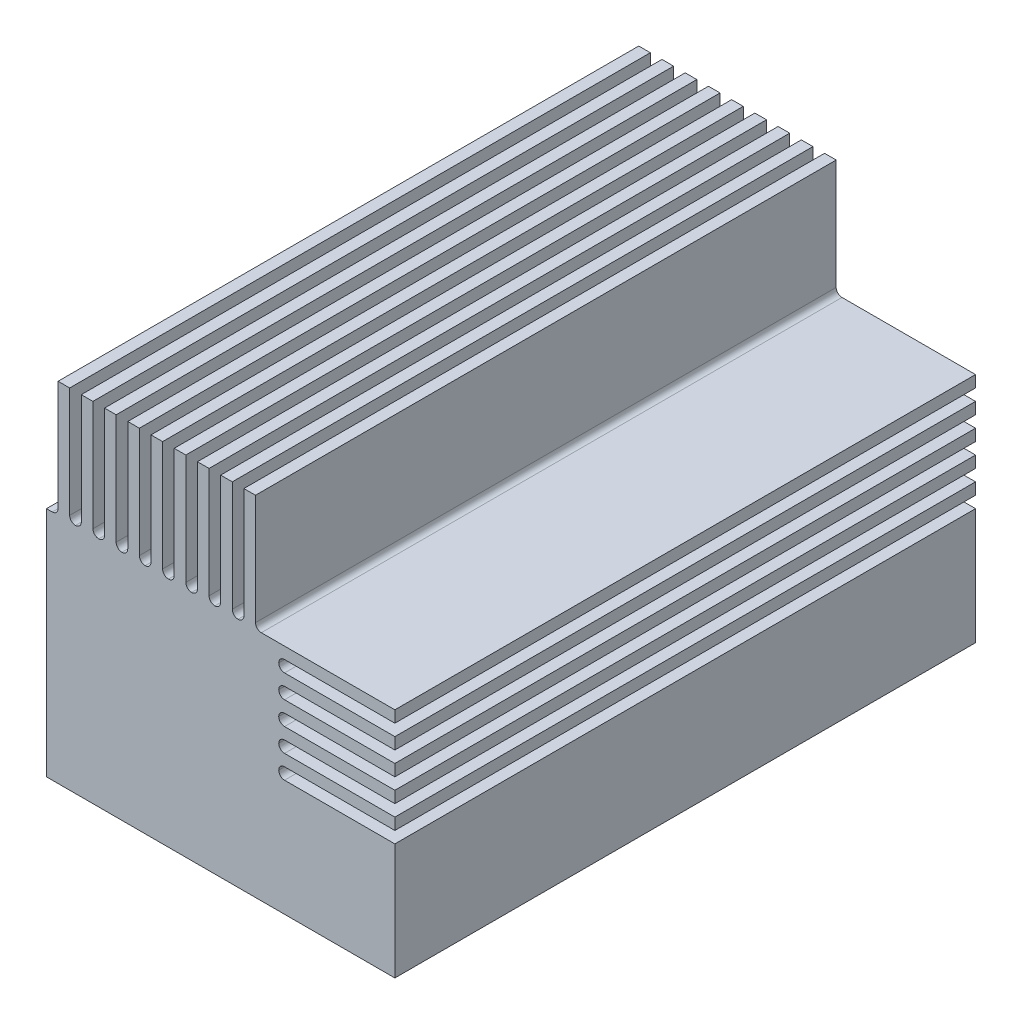
SolidWorks part; units mm, degrees
ref_plane "Front Plane" through (0, 0, 0) normal (0, 0, 1) x (1, 0, 0)
ref_plane "Top Plane" through (0, 0, 0) normal (0, 1, 0) x (1, 0, 0)
ref_plane "Right Plane" through (0, 0, 0) normal (1, 0, 0) x (0, 0, -1)
sketch "Sketch1" plane through (0, 0, 0) normal (0, 1, 0) x (1, 0, 0)
  line L1 (0, 0) -> (100, 0)
  line L2 (0, 0) -> (0, 250)
  line L3 (0, 250) -> (100, 250)
  line L4 (100, 0) -> (100, 250)
  dimension "D1" = 100
  dimension "D2" = 250
extrude "Boss-Extrude1" add sketch "Sketch1" along normal blind 100
sketch "Sketch2" plane through (0, 0, 0) normal (0, 0, 1) x (1, 0, 0)
  line L41 (100, 90) -> (100, 85)
  line L42 (100, 100) -> (150, 100)
  line L43 (100, 100) -> (100, 95)
  line L44 (100, 95) -> (150, 95)
  line L45 (150, 100) -> (150, 95)
  line L46 (100, 90) -> (150, 90)
  line L47 (150, 90) -> (150, 85)
  line L48 (100, 85) -> (150, 85)
  line L49 (100, 80) -> (100, 75)
  line L50 (100, 80) -> (150, 80)
  line L51 (150, 80) -> (150, 75)
  line L52 (100, 75) -> (150, 75)
  line L53 (100, 70) -> (100, 65)
  line L54 (0, 100) -> (5, 100) construction
  line L55 (0, 100) -> (100, 100) construction
  line L56 (15, 100) -> (15, 150)
  line L57 (5, 100) -> (10, 100)
  line L58 (5, 100) -> (5, 150)
  line L59 (5, 150) -> (10, 150)
  line L60 (10, 100) -> (10, 150)
  line L61 (15, 100) -> (20, 100)
  line L62 (20, 100) -> (20, 150)
  line L63 (15, 150) -> (20, 150)
  line L64 (25, 100) -> (25, 150)
  line L65 (25, 100) -> (30, 100)
  line L66 (30, 100) -> (30, 150)
  line L67 (25, 150) -> (30, 150)
  line L68 (35, 100) -> (35, 150)
  line L69 (35, 100) -> (40, 100)
  line L70 (40, 100) -> (40, 150)
  line L71 (35, 150) -> (40, 150)
  line L72 (45, 100) -> (45, 150)
  line L73 (45, 100) -> (50, 100)
  line L74 (50, 100) -> (50, 150)
  line L75 (45, 150) -> (50, 150)
  line L76 (55, 100) -> (55, 150)
  line L77 (55, 100) -> (60, 100)
  line L78 (60, 100) -> (60, 150)
  line L79 (55, 150) -> (60, 150)
  line L80 (65, 100) -> (65, 150)
  line L81 (65, 100) -> (70, 100)
  line L82 (70, 100) -> (70, 150)
  line L83 (65, 150) -> (70, 150)
  line L84 (75, 100) -> (75, 150)
  line L85 (75, 100) -> (80, 100)
  line L86 (80, 100) -> (80, 150)
  line L87 (75, 150) -> (80, 150)
  line L88 (85, 100) -> (85, 150)
  line L89 (85, 100) -> (90, 100)
  line L90 (90, 100) -> (90, 150)
  line L91 (85, 150) -> (90, 150)
  line L92 (100, 70) -> (150, 70)
  line L134 (150, 55) -> (150, 50) construction
  line L135 (100, 0) -> (150, 0)
  line L136 (100, 0) -> (100, 50)
  line L137 (100, 50) -> (150, 50)
  line L138 (150, 0) -> (150, 50)
  line L140 (150, 70) -> (150, 65)
  line L141 (100, 65) -> (150, 65)
  line L142 (100, 60) -> (100, 55)
  line L143 (100, 60) -> (150, 60)
  line L144 (150, 60) -> (150, 55)
  line L145 (100, 55) -> (150, 55)
  dimension "D1" = 5
  dimension "D2" = 50
  dimension "D4" = 5
  dimension "D3" = 50
  dimension "D5" = 5
  dimension "D6" = 5
  dimension "D7" = 5
extrude "Boss-Extrude2" add sketch "Sketch2" against normal up to surface (250 mm away) up to face at (50, 50, -250)
fillet "Fillet3" radius 2.5 18 edges at (10, 100, -125) (20, 100, -125) (30, 100, -125) (40, 100, -125) (50, 100, -125) (60, 100, -125) (70, 100, -125) (80, 100, -125) (90, 100, -125) (85, 100, -125) (75, 100, -125) (65, 100, -125) (55, 100, -125) (45, 100, -125) (35, 100, -125) (25, 100, -125) (15, 100, -125) (5, 100, -125)
fillet "Fillet4" radius 2.5 10 edges at (100, 55, -125) (100, 65, -125) (100, 75, -125) (100, 85, -125) (100, 95, -125) (100, 90, -125) (100, 80, -125) (100, 70, -125) (100, 60, -125) (100, 50, -125)
